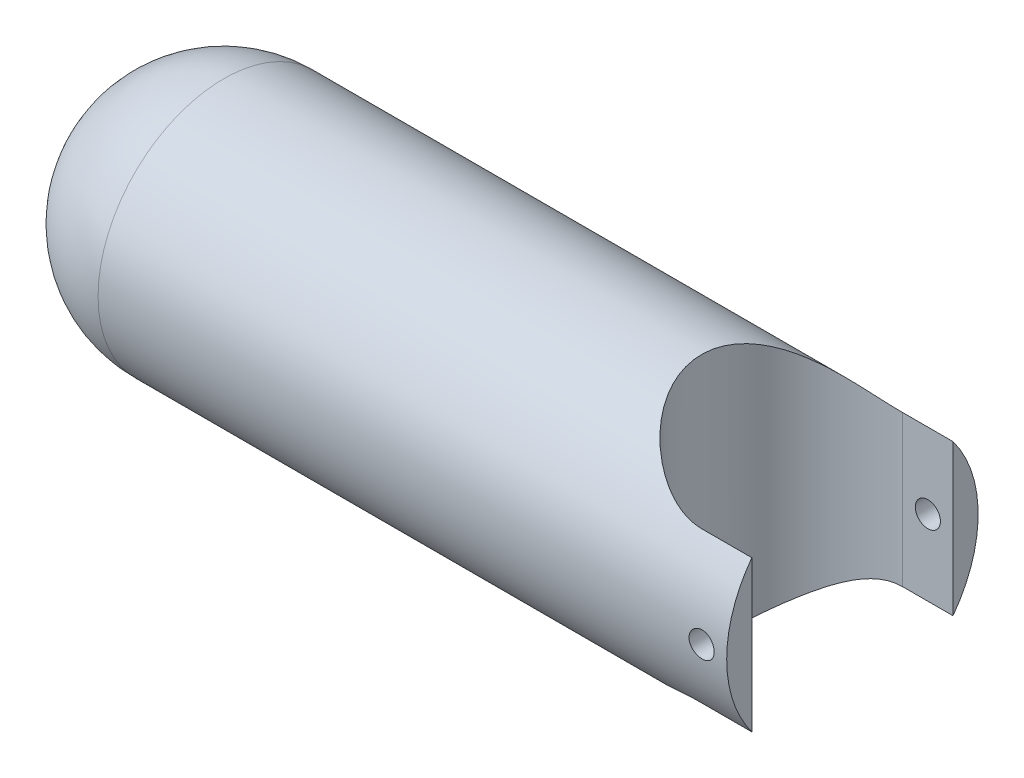
SolidWorks part; units mm, degrees
material "Aleación 2014"
ref_plane "Alzado" through (0, 0, 0) normal (0, 0, 1) x (1, 0, 0)
ref_plane "Planta" through (0, 0, 0) normal (0, 1, 0) x (1, 0, 0)
ref_plane "Vista lateral" through (0, 0, 0) normal (1, 0, 0) x (0, 0, -1)
sketch "Croquis3" plane through (0, 0, 0) normal (0, 1, 0) x (1, 0, 0)
  line L2 (11.918, 0) -> (36.918, 0) construction
  line L5 (11.918, 0) -> (161.918, 0)
  line L17 (161.918, 0) -> (161.918, 25)
  line L19 (36.918, 25) -> (161.918, 25)
  arc A4 (36.918, 25) -> (11.918, 0) centre (36.918, 0) ccw
  dimension "D2" = 150
  dimension "D3" = 125
  dimension "D1" = 25
revolve "Revolución10" add sketch "Croquis3" angle 360 about L5
sketch "Croquis6" plane through (0, 0, 0) normal (0, 0, 1) x (1, 0, 0)
  circle A4 centre (156.918, 0) radius 2.5
extrude "Cortar-Extruir1" cut sketch "Croquis6" against normal through all both and the other way through all
sketch "Croquis9" plane through (0, 0, 0) normal (0, 1, 0) x (1, 0, 0)
  line L2 (161.918, 20) -> (161.918, -20)
  line L6 (151.918, 20) -> (161.918, 20)
  line L7 (151.918, -20) -> (161.918, -20)
  arc A0 (151.918, 20) -> (151.918, -20) centre (151.918, 0) ccw
  dimension "D2" = 40
extrude "Cortar-Extruir3" cut sketch "Croquis9" against normal through all both and the other way through all contours L2 L7 A0 L6
